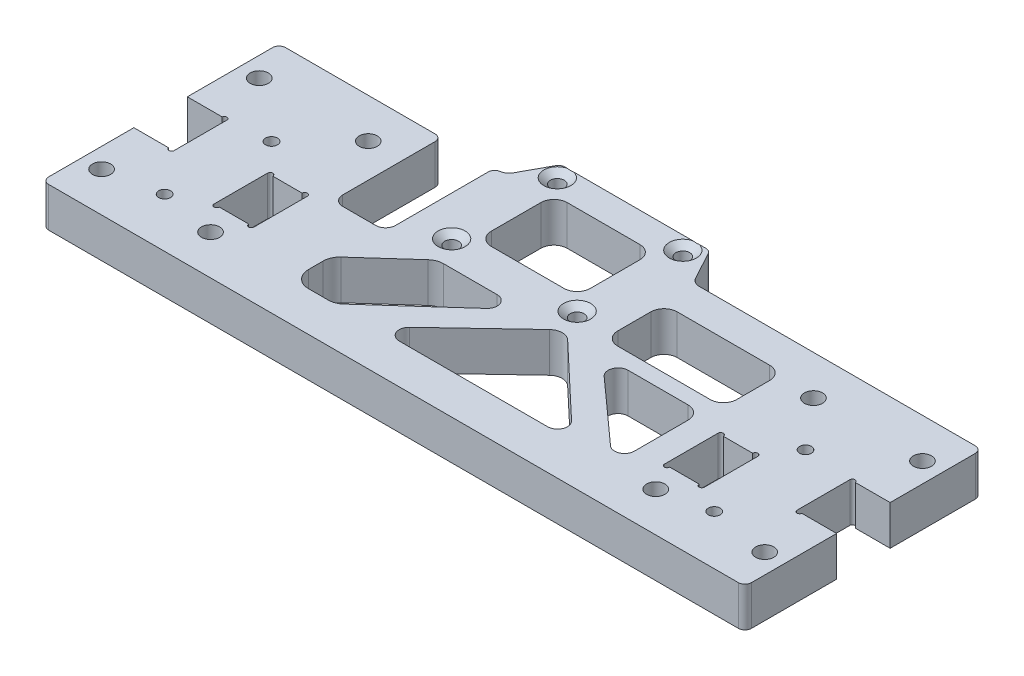
SolidWorks part; units mm, degrees
material "6061 Alloy"
ref_plane "Front Plane" through (0, 0, 0) normal (0, 0, 1) x (1, 0, 0)
ref_plane "Top Plane" through (0, 0, 0) normal (0, 1, 0) x (1, 0, 0)
ref_plane "Right Plane" through (0, 0, 0) normal (1, 0, 0) x (0, 0, -1)
sketch "Sketch1" plane through (0, 0, 0) normal (0, 1, 0) x (1, 0, 0)
  line L0 (106.4, 76.65) -> (106.4, 0) construction
  line L6 (32.15, 36.1) -> (32.15, 19.9)
  line L8 (44.25, 36.1) -> (44.25, 19.9)
  line L13 (0, 71.75) -> (68.4, 71.75)
  line L14 (68.4, 71.75) -> (74.4, 82.75)
  line L15 (74.4, 82.75) -> (119.4, 82.75)
  line L16 (119.4, 82.75) -> (125.4, 71.75)
  line L17 (125.4, 71.75) -> (212.8, 71.75)
  line L18 (32.15, 28) -> (44.25, 28) construction
  line L19 (33.75, 36.1) -> (42.65, 36.1)
  line L20 (33.75, 19.9) -> (42.65, 19.9)
  line L21 (180.65, 36.1) -> (180.65, 19.9)
  line L22 (179.05, 36.1) -> (170.15, 36.1)
  line L23 (168.55, 36.1) -> (168.55, 19.9)
  line L24 (179.05, 19.9) -> (170.15, 19.9)
  line L25 (12.1, 35.875) -> (0, 35.875) construction
  line L29 (12.1, 43.975) -> (12.1, 27.775)
  line L30 (10.5189, 43.975) -> (0, 43.975)
  line L31 (10.5189, 27.775) -> (0, 27.775)
  line L32 (0, 27.775) -> (0, 0)
  line L33 (0, 43.975) -> (0, 71.75)
  line L34 (200.7, 35.875) -> (212.8, 35.875) construction
  line L35 (212.8, 43.975) -> (212.8, 71.75)
  line L36 (212.8, 27.775) -> (212.8, 0)
  line L37 (202.2811, 27.775) -> (212.8, 27.775)
  line L38 (202.2811, 43.975) -> (212.8, 43.975)
  line L39 (200.7, 43.975) -> (200.7, 27.775)
  line L44 (106.4, 0) -> (212.8, 0)
  line L46 (106.4, 0) -> (0, 0)
  circle A0 centre (39, 59.75) radius 2.75
  circle A5 centre (39, 12) radius 2.75
  circle A6 centre (173.8, 59.75) radius 2.75
  circle A7 centre (173.8, 12) radius 2.75
  arc A8 (32.15, 36.1) -> (33.75, 36.1) centre (32.95, 36.1) cw
  arc A9 (44.25, 36.1) -> (42.65, 36.1) centre (43.45, 36.1) ccw
  arc A10 (32.15, 19.9) -> (33.75, 19.9) centre (32.95, 19.9) ccw
  arc A11 (44.25, 19.9) -> (42.65, 19.9) centre (43.45, 19.9) cw
  arc A12 (180.65, 19.9) -> (179.05, 19.9) centre (179.85, 19.9) cw
  arc A13 (180.65, 36.1) -> (179.05, 36.1) centre (179.85, 36.1) ccw
  arc A14 (168.55, 36.1) -> (170.15, 36.1) centre (169.35, 36.1) cw
  arc A15 (168.55, 19.9) -> (170.15, 19.9) centre (169.35, 19.9) ccw
  circle A16 centre (6, 12) radius 2.75
  circle A17 centre (6, 59.75) radius 2.75
  arc A18 (12.1, 27.775) -> (10.5189, 27.775) centre (11.3095, 27.8976) cw
  arc A19 (12.1, 43.975) -> (10.5189, 43.975) centre (11.3095, 43.8524) ccw
  arc A20 (200.7, 43.975) -> (202.2811, 43.975) centre (201.4905, 43.8524) cw
  arc A21 (200.7, 27.775) -> (202.2811, 27.775) centre (201.4905, 27.8976) ccw
  circle A22 centre (206.8, 59.75) radius 2.75
  circle A23 centre (206.8, 12) radius 2.75
  dimension "D12" = 5.5
  dimension "D16" = 5.5
  dimension "D17" = 0.8
  dimension "D18" = 0.8
  dimension "D19" = 0.8
  dimension "D20" = 0.8
  dimension "D21" = 5.5
  dimension "D22" = 5.5
  dimension "D27" = 0.8
  dimension "D1" = 212.8
  dimension "D2" = 71.75
  dimension "D5" = 62.15
  dimension "D6" = 12.1
  dimension "D4" = 11
  dimension "D7" = 6
  dimension "D8" = 38
  dimension "D10" = 45
  dimension "D11" = 16.2
  dimension "D14" = 6
  dimension "D13" = 12
  dimension "D25" = 16.2
  dimension "D3" = 12
  dimension "D23" = 16.2
  dimension "D26" = 12.1
  dimension "D9" = 6
  dimension "D15" = 6
  dimension "D24" = 33
  dimension "D28" = 33
  dimension "D29" = 0
  dimension "D30" = 0
  dimension "D31" = 0
extrude "Boss-Extrude1" add sketch "Sketch1" along normal blind 12
sketch "Sketch2" plane through (0, 12, 0) normal (0, 1, 0) x (1, 0, 0)
  line L1 (49.25, 85.2461) -> (65.25, 85.2461)
  line L2 (49.25, 85.2461) -> (49.25, 38.75)
  line L3 (49.25, 38.75) -> (65.25, 38.75)
  line L4 (65.25, 85.2461) -> (65.25, 38.75)
  line L5 (44.25, 19.9) -> (44.25, 36.1) construction
  line L12 (68.4, 71.75) -> (0, 71.75) construction
  dimension "D1" = 5
  dimension "D2" = 16
  dimension "D3" = 33
extrude "Cut-Extrude1" cut sketch "Sketch2" against normal through all
sketch "Sketch3" plane through (0, 12, 0) normal (0, 1, 0) x (1, 0, 0)
  line L1 (65.25, 38.75) -> (65.25, 71.75) construction
  line L2 (119.4, 82.75) -> (74.4, 82.75) construction
  circle A0 centre (77.25, 78.75) radius 2.1
  circle A1 centre (77.25, 46.75) radius 2.1
  circle A2 centre (115.25, 78.75) radius 2.1
  circle A3 centre (115.25, 46.75) radius 2.1
  dimension "D2" = 4.2
  dimension "D5" = 4.2
  dimension "D8" = 32
  dimension "D1" = 4
  dimension "D3" = 12
  dimension "D4" = 32
  dimension "D7" = 38
  dimension "D6" = 2
extrude "Cut-Extrude2" cut sketch "Sketch3" against normal through all
sketch "Sketch5" plane through (0, 12, 0) normal (0, 1, 0) x (1, 0, 0)
  line L3 (98.7821, 39) -> (82.5187, 39)
  line L11 (78.0261, 13.2835) -> (100.789, 33.7701)
  line L12 (65.25, 38.75) -> (65.25, 71.75) construction
  line L13 (115.8513, 37.7761) -> (94.0759, 17.1795)
  line L14 (118.6, 40.376) -> (118.6, 12) construction
  line L15 (96.1374, 12) -> (141.0626, 12)
  line L16 (121.3487, 37.7761) -> (143.1241, 17.1795)
  line L17 (138.4179, 39) -> (156.6, 39)
  line L18 (155.5931, 16.5062) -> (136.411, 33.7701)
  line L19 (160.6, 35) -> (160.6, 18.7361)
  line L20 (119.4, 82.75) -> (74.4, 82.75) construction
  line L21 (85.25, 73.75) -> (107.25, 73.75)
  line L22 (81.25, 69.75) -> (81.25, 54.75)
  line L23 (85.25, 50.75) -> (107.25, 50.75)
  line L24 (111.25, 69.75) -> (111.25, 54.75)
  line L25 (212.8, 71.75) -> (125.4, 71.75) construction
  line L26 (130.55, 61.75) -> (158.55, 61.75)
  line L27 (126.55, 57.75) -> (126.55, 47.75)
  line L28 (130.55, 43.75) -> (158.55, 43.75)
  line L29 (162.55, 57.75) -> (162.55, 47.75)
  line L30 (79.1739, 37.7165) -> (65.279, 25.2111)
  line L31 (168.55, 36.1) -> (168.55, 19.9) construction
  line L32 (63.6239, 21.4947) -> (63.6239, 17)
  line L33 (68.6239, 12) -> (74.6813, 12)
  arc A0 (121.3487, 37.7761) -> (115.8513, 37.7761) centre (118.6, 34.8701) ccw
  arc A1 (160.6, 35) -> (156.6, 39) centre (156.6, 35) ccw
  arc A3 (111.25, 69.75) -> (107.25, 73.75) centre (107.25, 69.75) ccw
  arc A4 (107.25, 50.75) -> (111.25, 54.75) centre (107.25, 54.75) ccw
  arc A5 (81.25, 54.75) -> (85.25, 50.75) centre (85.25, 54.75) ccw
  arc A6 (81.25, 69.75) -> (85.25, 73.75) centre (85.25, 69.75) cw
  arc A7 (155.5931, 16.5062) -> (160.6, 18.7361) centre (157.6, 18.7361) ccw
  arc A8 (136.411, 33.7701) -> (138.4179, 39) centre (138.4179, 36) cw
  arc A10 (141.0626, 12) -> (143.1241, 17.1795) centre (141.0626, 15) ccw
  arc A11 (96.1374, 12) -> (94.0759, 17.1795) centre (96.1374, 15) cw
  arc A12 (100.789, 33.7701) -> (98.7821, 39) centre (98.7821, 36) ccw
  arc A13 (162.55, 57.75) -> (158.55, 61.75) centre (158.55, 57.75) ccw
  arc A14 (158.55, 43.75) -> (162.55, 47.75) centre (158.55, 47.75) ccw
  arc A15 (126.55, 47.75) -> (130.55, 43.75) centre (130.55, 47.75) ccw
  arc A16 (126.55, 57.75) -> (130.55, 61.75) centre (130.55, 57.75) cw
  arc A17 (79.1739, 37.7165) -> (82.5187, 39) centre (82.5187, 34) cw
  arc A18 (63.6239, 21.4947) -> (65.279, 25.2111) centre (68.6239, 21.4947) cw
  arc A19 (68.6239, 12) -> (63.6239, 17) centre (68.6239, 17) cw
  arc A20 (74.6813, 12) -> (78.0261, 13.2835) centre (74.6813, 17) ccw
  point P25 (160.6, 39)
  point P33 (111.25, 50.75)
  point P36 (81.25, 50.75)
  point P39 (81.25, 73.75)
  point P42 (160.6, 12)
  point P45 (130.6, 39)
  point P48 (76.6, 12)
  point P51 (148.6, 12)
  point P54 (88.6, 12)
  point P57 (106.6, 39)
  point P68 (162.55, 61.75)
  point P71 (162.55, 43.75)
  point P76 (126.55, 61.75)
  dimension "D11" = 4
  dimension "D12" = 3
  dimension "D13" = 3
  dimension "D14" = 3
  dimension "D19" = 4
  dimension "D2" = 5
  dimension "D4" = 5
  dimension "D3" = 12
  dimension "D6" = 30
  dimension "D7" = 9
  dimension "D8" = 16
  dimension "D9" = 23
  dimension "D10" = 30
  dimension "D15" = 10
  dimension "D16" = 18
  dimension "D17" = 6
  dimension "D18" = 36
extrude "Cut-Extrude3" cut sketch "Sketch5" against normal through all
fillet "Fillet1" radius 3 4 edges at (68.4, 6, -71.75) (65.25, 6, -38.75) (49.25, 6, -38.75) (125.4, 6, -71.75)
fillet "Fillet2" radius 2 8 edges at (212.8, 6, -71.75) (119.4, 6, -82.75) (74.4, 6, -82.75) (49.25, 6, -71.75) (65.25, 6, -71.75) (0, 6, -71.75) (212.8, 6, 0) (0, 6, 0)
sketch "Sketch6" plane through (0, 12, 0) normal (0, 1, 0) x (1, 0, 0)
  line L0 (2, 0) -> (210.8, 0) construction
  line L1 (105.3, 92.584) -> (105.3, -38.973) construction
  line L2 (212.8, 2) -> (212.8, 27.775) construction
  circle A0 centre (186.15, 45) radius 1.8
  circle A1 centre (173.8, 59.75) radius 2.75 construction
  circle A2 centre (188.5, 15) radius 1.8
  circle A3 centre (24.45, 45) radius 1.8
  circle A4 centre (22.1, 15) radius 1.8
  dimension "D2" = 3.6
  dimension "D5" = 3.6
  dimension "D1" = 12.35
  dimension "D3" = 45
  dimension "D4" = 15
  dimension "D6" = 107.5
extrude "Cut-Extrude4" cut sketch "Sketch6" against normal through all
chamfer "Chamfer1" distance 2 angle 40 4 edges at (115.25, 12, -76.65) (115.25, 12, -44.65) (77.25, 12, -44.65) (77.25, 12, -76.65) first distance on face at (188.5, 12, -13.2)
equation "\"DriveMotorLength\"= 90mm"
equation "\"DriveMotorGap\"= 10mm"
equation "\"AluminumThickness\"= 0.5in"
equation "\"ChassisWidth\"= ( \"DriveMotorLength\" + \"AluminumThickness\" ) * 2 + \"DriveMotorGap\""
equation "\"RepeatMagnumHoleWidth\"= 19.05mm"
equation "\"MortiseWidth\"= 16mm"
equation "\"ChassisScrewThruHole\"= 5.5mm"
equation "\"D11@Sketch1\"=\"MortiseSlotWidth\""
equation "\"D12@Sketch1\"=\"ChassisScrewThruHole\""
equation "\"D16@Sketch1\"=\"ChassisScrewThruHole\""
equation "\"MortiseSlotWidth\"= 16.2mm"
equation "\"Dogbone\"= 0.8mm"
equation "\"D17@Sketch1\"=\"Dogbone\""
equation "\"D18@Sketch1\"=\"Dogbone\""
equation "\"D19@Sketch1\"=\"Dogbone\""
equation "\"D20@Sketch1\"=\"Dogbone\""
equation "\"D21@Sketch1\"=\"ChassisScrewThruHole\""
equation "\"D22@Sketch1\"=\"ChassisScrewThruHole\""
equation "\"D27@Sketch1\"=\"Dogbone\""
equation "\"D23@Sketch1\"=\"MortiseSlotWidth\""
equation "\"D25@Sketch1\"=\"MortiseSlotWidth\""
